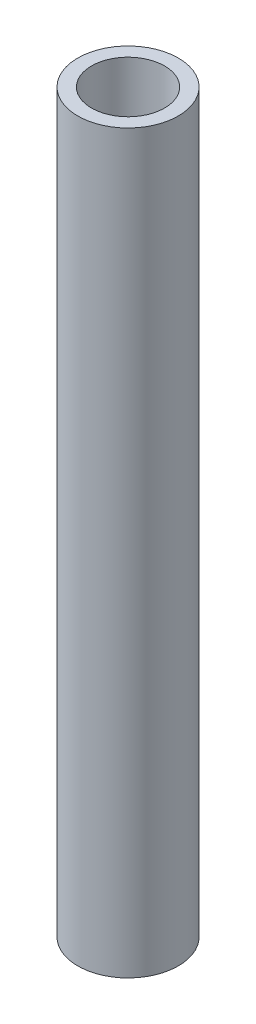
SolidWorks part; units mm, degrees
ref_plane "Front Plane" through (0, 0, 0) normal (0, 0, 1) x (1, 0, 0)
ref_plane "Top Plane" through (0, 0, 0) normal (0, 1, 0) x (1, 0, 0)
ref_plane "Right Plane" through (0, 0, 0) normal (1, 0, 0) x (0, 0, -1)
sketch "Sketch1" plane through (0, 0, 0) normal (0, 1, 0) x (1, 0, 0)
  circle A0 centre (0, 0) radius 2.58
  circle A1 centre (0, 0) radius 3.55
  dimension "D1" = 5.16
extrude "Boss-Extrude1" add sketch "Sketch1" along normal blind 52
